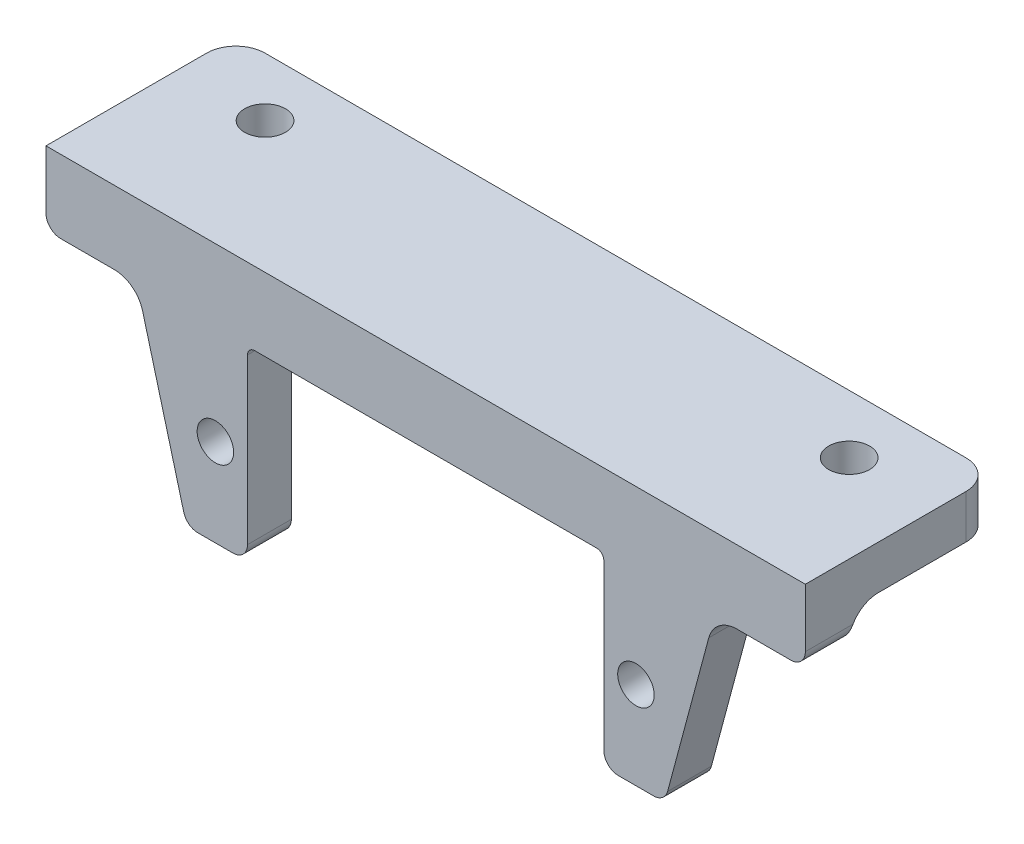
SolidWorks part; units mm, degrees
ref_plane "Front Plane" through (0, 0, 0) normal (0, 0, 1) x (1, 0, 0)
ref_plane "Top Plane" through (0, 0, 0) normal (0, 1, 0) x (1, 0, 0)
ref_plane "Right Plane" through (0, 0, 0) normal (1, 0, 0) x (0, 0, -1)
sketch "Sketch1" plane through (0, 0, 0) normal (0, 0, 1) x (1, 0, 0)
  line L1 (-15.9, -6.25) -> (15.9, -6.25)
  line L2 (-15.9, -6.25) -> (-15.9, 6.25)
  line L3 (-15.9, 6.25) -> (15.9, 6.25)
  line L4 (15.9, -6.25) -> (15.9, 6.25)
  line L5 (-15.9, -6.25) -> (15.9, 6.25) construction
  line L6 (-15.9, 6.25) -> (15.9, -6.25) construction
  line L7 (11.7, -6.25) -> (-11.7, -6.25)
  line L8 (11.7, -6.25) -> (11.7, 6.25)
  line L9 (11.7, 6.25) -> (-11.7, 6.25)
  line L10 (-11.7, -6.25) -> (-11.7, 6.25)
  line L11 (11.7, -6.25) -> (-11.7, 6.25) construction
  line L12 (11.7, 6.25) -> (-11.7, -6.25) construction
  circle A0 centre (-14.4, 0) radius 1
  circle A1 centre (-14.4, 3.5) radius 1
  circle A2 centre (-14.4, -3.5) radius 1
  circle A3 centre (14.4, 0) radius 1
  circle A4 centre (14.4, 3.5) radius 1
  circle A5 centre (14.4, -3.5) radius 1
  point P0 (0, 0)
  point P20 (0, 0)
  dimension "D3" = 2
  dimension "D1" = 31.8
  dimension "D2" = 12.5
  dimension "D4" = 1.5
  dimension "D5" = 3.5
  dimension "D6" = 3.5
  dimension "D7" = 1.5
  dimension "D8" = 23.4
sketch "Sketch3" plane through (0, 0, 0) normal (0, 0, 1) x (1, 0, 0)
  line L0 (-12.2, 6.25) -> (-12.2, -5)
  line L1 (-11.7, -6.25) -> (-11.7, 6.25) construction
  line L2 (-13.2, -6) -> (-15.6, -6)
  line L3 (-16.5659, -5.2588) -> (-19.3865, 5.2676)
  line L4 (12.2, 6.25) -> (12.2, -5)
  line L5 (11.7, -6.25) -> (11.7, 6.25) construction
  line L6 (13.2, -6) -> (15.6, -6)
  line L7 (16.5659, -5.2588) -> (19.3865, 5.2676)
  line L8 (-11.7, 6.75) -> (11.7, 6.75)
  line L9 (-15.9, 6.25) -> (15.9, 6.25) construction
  line L12 (-26, 11.75) -> (26, 11.75)
  line L14 (-21.3183, 6.75) -> (-25, 6.75)
  line L15 (-26, 7.75) -> (-26, 11.75)
  line L16 (21.3183, 6.75) -> (25, 6.75)
  line L17 (26, 7.75) -> (26, 11.75)
  circle A0 centre (-14.4, 0) radius 1.25
  circle A1 centre (14.4, 0) radius 1.25
  arc A2 (-12.2, -5) -> (-13.2, -6) centre (-13.2, -5) cw
  arc A3 (-15.6, -6) -> (-16.5659, -5.2588) centre (-15.6, -5) cw
  arc A4 (13.2, -6) -> (12.2, -5) centre (13.2, -5) cw
  arc A5 (16.5659, -5.2588) -> (15.6, -6) centre (15.6, -5) cw
  arc A6 (-11.7, 6.75) -> (-12.2, 6.25) centre (-11.7, 6.25) ccw
  arc A7 (12.2, 6.25) -> (11.7, 6.75) centre (11.7, 6.25) ccw
  arc A8 (-19.3865, 5.2676) -> (-21.3183, 6.75) centre (-21.3183, 4.75) ccw
  arc A9 (21.3183, 6.75) -> (19.3865, 5.2676) centre (21.3183, 4.75) ccw
  arc A10 (-25, 6.75) -> (-26, 7.75) centre (-25, 7.75) cw
  arc A11 (26, 7.75) -> (25, 6.75) centre (25, 7.75) cw
  point P16 (14.4, -6)
  point P22 (-12.2, -6)
  point P25 (-16.3673, -6)
  point P27 (-14.4, -6)
  point P30 (12.2, -6)
  point P46 (-19.7837, 6.75)
  point P49 (19.7837, 6.75)
  dimension "D1" = 2.5
  dimension "D9" = 1
  dimension "D10" = 1
  dimension "D11" = 1
  dimension "D6" = 1
  dimension "D12" = 0.5
  dimension "D13" = 0.5
  dimension "D14" = 2
  dimension "D15" = 2
  dimension "D16" = 1
  dimension "D17" = 1
  dimension "D2" = 0.5
  dimension "D3" = 75
  dimension "D4" = 0.5
  dimension "D8" = 0.5
  dimension "D5" = 6
  dimension "D7" = 75
  dimension "D19" = 5
  dimension "D18" = 52
extrude "Boss-Extrude1" add sketch "Sketch3" along normal blind 3
sketch "Sketch4" plane through (0, 0, 0) normal (0, 0, -1) x (-1, 0, 0)
  line L2 (26, 11.75) -> (26, 7.75) construction
  line L3 (-26, 11.75) -> (26, 11.75)
  line L4 (-26, 11.75) -> (-26, 8.75)
  line L5 (-26, 8.75) -> (26, 8.75)
  line L6 (26, 11.75) -> (26, 8.75)
  point P9 (-26, 8.75)
  point P12 (26, 8.75)
  dimension "D1" = 3
extrude "Boss-Extrude2" add sketch "Sketch4" along normal blind 10
fillet "Fillet1" radius 2 1 edges at (0, 8.75, 0)
fillet "Fillet2" radius 2 2 edges at (-26, 10.25, -10) (26, 10.25, -10)
sketch "Sketch5" plane through (0, 8.75, 0) normal (0, -1, 0) x (1, 0, 0)
  line L0 (-26, -8) -> (-26, -2) construction
  line L2 (24, -10) -> (-24, -10) construction
  circle A0 centre (-20, -6) radius 1.4
  dimension "D1" = 2.8
  dimension "D2" = 6
  dimension "D3" = 4
extrude "Cut-Extrude1" cut sketch "Sketch5" against normal through all
mirror "Mirror1" about plane through (0, 0, 0) normal (1, 0, 0) of "Cut-Extrude1"
equation "\"D6@Sketch1\"=\"D5@Sketch1\""
equation "\"D7@Sketch1\"=\"D4@Sketch1\""
equation "\"D4@Sketch3\"=\"D2@Sketch3\""
equation "\"D8@Sketch3\"=\"D2@Sketch3\""
